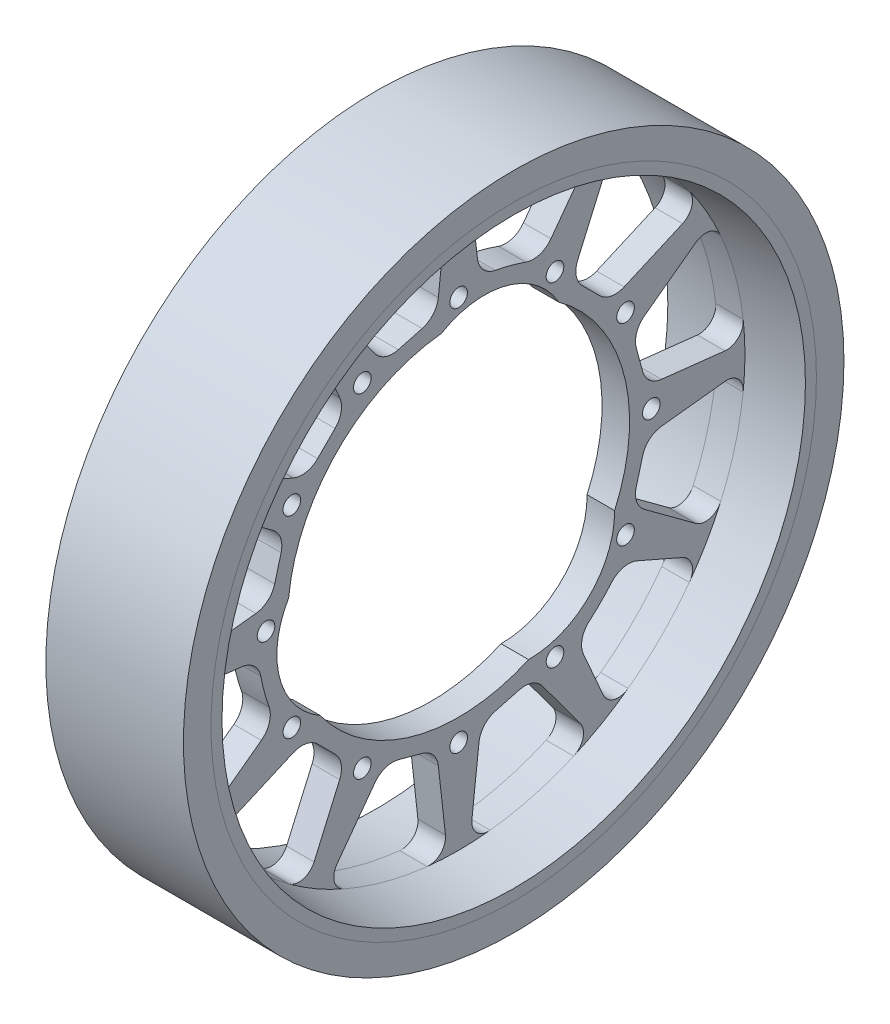
SolidWorks part; units mm, degrees
material "6063-T6"
ref_plane "前视基准面" through (0, 0, 0) normal (0, 0, 1) x (1, 0, 0)
ref_plane "上视基准面" through (0, 0, 0) normal (0, 1, 0) x (1, 0, 0)
ref_plane "右视基准面" through (0, 0, 0) normal (1, 0, 0) x (0, 0, -1)
sketch "草图1" plane through (0, 0, 0) normal (0, 0, 1) x (1, 0, 0)
  line L0 (0, 0) -> (0, 55) construction
  line L2 (-12.5, 55) -> (-12.5, 53)
  line L3 (-12.5, 53) -> (-2.5, 52)
  line L4 (-2.5, 52) -> (-2.5, 31.05)
  line L5 (-2.5, 31.05) -> (2.5, 31.05)
  line L6 (0, 0) -> (-48.4134, 0) construction
  line L7 (-12.5, 55) -> (12.5, 55)
  line L8 (2.5, 52) -> (2.5, 31.05)
  line L9 (12.5, 53) -> (2.5, 52)
  line L10 (12.5, 55) -> (12.5, 53)
  point P12 (0, 55)
  point P13 (0, 31.05)
  dimension "D1" = 62.1
  dimension "D2" = 110
  dimension "D4" = 2
  dimension "D5" = 3
  dimension "D6" = 5
  dimension "D7" = 25
revolve "旋转1" add sketch "草图1" angle 360 about L6
sketch "草图2" plane through (2.5, 0, 0) normal (1, 0, 0) x (0, 0, -1)
  circle A0 centre (0, 0) radius 35 construction
  circle A1 centre (0, 35) radius 1.6
  circle A2 centre (17.5, 30.3109) radius 1.6
  circle A3 centre (30.3109, 17.5) radius 1.6
  circle A4 centre (35, 0) radius 1.6
  circle A5 centre (30.3109, -17.5) radius 1.6
  circle A6 centre (17.5, -30.3109) radius 1.6
  circle A7 centre (0, -35) radius 1.6
  circle A8 centre (-17.5, -30.3109) radius 1.6
  circle A9 centre (-30.3109, -17.5) radius 1.6
  circle A10 centre (-35, 0) radius 1.6
  circle A11 centre (-30.3109, 17.5) radius 1.6
  circle A12 centre (-17.5, 30.3109) radius 1.6
  point P29 (0, 0)
  dimension "D1" = 70
  dimension "D2" = 3.2
  dimension "D3" = 12
extrude "切除-拉伸1" cut sketch "草图2" against normal through all
sketch "草图3" plane through (0, 0, 0) normal (0, 0, 1) x (1, 0, 0)
  line L0 (12.5, -55) -> (12.5, 55) construction
  line L1 (-12.5, 55) -> (12.5, 55)
  line L2 (-12.5, 55) -> (-12.5, 60)
  line L3 (-12.5, 60) -> (12.5, 60)
  line L4 (12.5, 55) -> (12.5, 60)
  line L5 (0, 0) -> (-74.3515, 0) construction
  dimension "D1" = 5
revolve "旋转2" add sketch "草图3" angle 360 about L5
sketch "草图4" plane through (2.5, 0, 0) normal (1, 0, 0) x (0, 0, -1)
  line L0 (0, 0) -> (0, 52) construction
  line L1 (0, 0) -> (26, 45.0333) construction
  line L2 (2.4029, 48.3689) -> (3.6959, 36.8393)
  line L3 (6.6357, 33.4214) -> (10.964, 32.2616)
  line L4 (15.2189, 33.7517) -> (22.1035, 43.0902)
  line L5 (8.7998, 32.8415) -> (0, 0) construction
  circle A0 centre (0, 0) radius 52 construction
  arc A1 (20.8942, 47.6176) -> (5.7138, 51.6851) centre (0, 0) ccw
  arc A2 (10.964, 32.2616) -> (15.2189, 33.7517) centre (11.9993, 36.1253) ccw
  arc A3 (3.6959, 36.8393) -> (6.6357, 33.4214) centre (7.671, 37.2851) ccw
  arc A4 (22.1035, 43.0902) -> (20.8942, 47.6176) centre (19.6888, 44.8704) ccw
  arc A5 (2.4029, 48.3689) -> (5.7138, 51.6851) centre (5.3842, 48.7033) cw
  point P6 (17.5, 30.3109)
  point P19 (13.5997, 31.5554)
  point P22 (4, 34.1276)
  point P24 (24.2487, 46)
  point P27 (2, 51.9615)
  dimension "D6" = 4
  dimension "D7" = 3
  dimension "D1" = 4
  dimension "D2" = 4
  dimension "D3" = 8
  dimension "D4" = 8
  dimension "D5" = 34
extrude "切除-拉伸2" cut sketch "草图4" against normal through all
pattern_circular "阵列(圆周)1" count 12 over 360 about axis through (0, 0, 0) along (1, 0, 0) of "切除-拉伸2"
sketch "草图5" plane through (2.5, 0, 0) normal (1, 0, 0) x (0, 0, -1)
  line L0 (0, 35) -> (17.5, 30.3109) construction
  line L1 (8.75, 32.6554) -> (0, 0) construction
  circle A0 centre (0, 0) radius 18.15 construction
  circle A1 centre (4.6976, 17.5316) radius 15.5
  circle A2 centre (12.834, -12.834) radius 15.5
  circle A3 centre (-17.5316, -4.6976) radius 15.5
  point P16 (0, 0)
  dimension "D1" = 36.3
  dimension "D2" = 31
  dimension "D3" = 3
extrude "切除-拉伸3" cut sketch "草图5" against normal blind 10
sketch "草图6" plane through (2.5, 0, 0) normal (1, 0, 0) x (0, 0, -1)
  line L0 (6.6357, 33.4214) -> (10.964, 32.2616) construction
  line L1 (6.6357, 33.4214) -> (10.964, 32.2616)
  arc A0 (14.9026, 33.3739) -> (3.7809, 36.3539) centre (0, 0) ccw
  arc A1 (3.6959, 36.8393) -> (6.6357, 33.4214) centre (7.671, 37.2851) ccw construction
  arc A2 (10.964, 32.2616) -> (15.2189, 33.7517) centre (11.9993, 36.1253) ccw construction
  arc A3 (3.7809, 36.3539) -> (6.6357, 33.4214) centre (7.671, 37.2851) ccw
  arc A4 (10.964, 32.2616) -> (14.9026, 33.3739) centre (11.9993, 36.1253) ccw
  arc A5 (-3.1672, 30.888) -> (-30.888, 3.1672) centre (0, 0) ccw construction
  dimension "D1" = 5.5
extrude "凸台-拉伸1" add sketch "草图6" against normal up to surface (5 mm away) up to face at (-2.5, 0, 0)
pattern_circular "阵列(圆周)6" count 3 over 360 about axis through (0, 0, 0) along (1, 0, 0) of "凸台-拉伸1"
fillet "圆角1" radius 4 6 edges at (0, 33.3739, -14.9026) (0, 36.3539, -3.7809) (0, -29.593, -21.4513) (0, -21.4513, -29.593) (0, -14.9026, 33.3739) (0, -3.7809, 36.3539)
move or copy body "实体-移动/复制2" [suppressed] bodies to move or copy 108 113
move or copy body "实体-移动/复制1" [suppressed] bodies to move or copy 108 113
